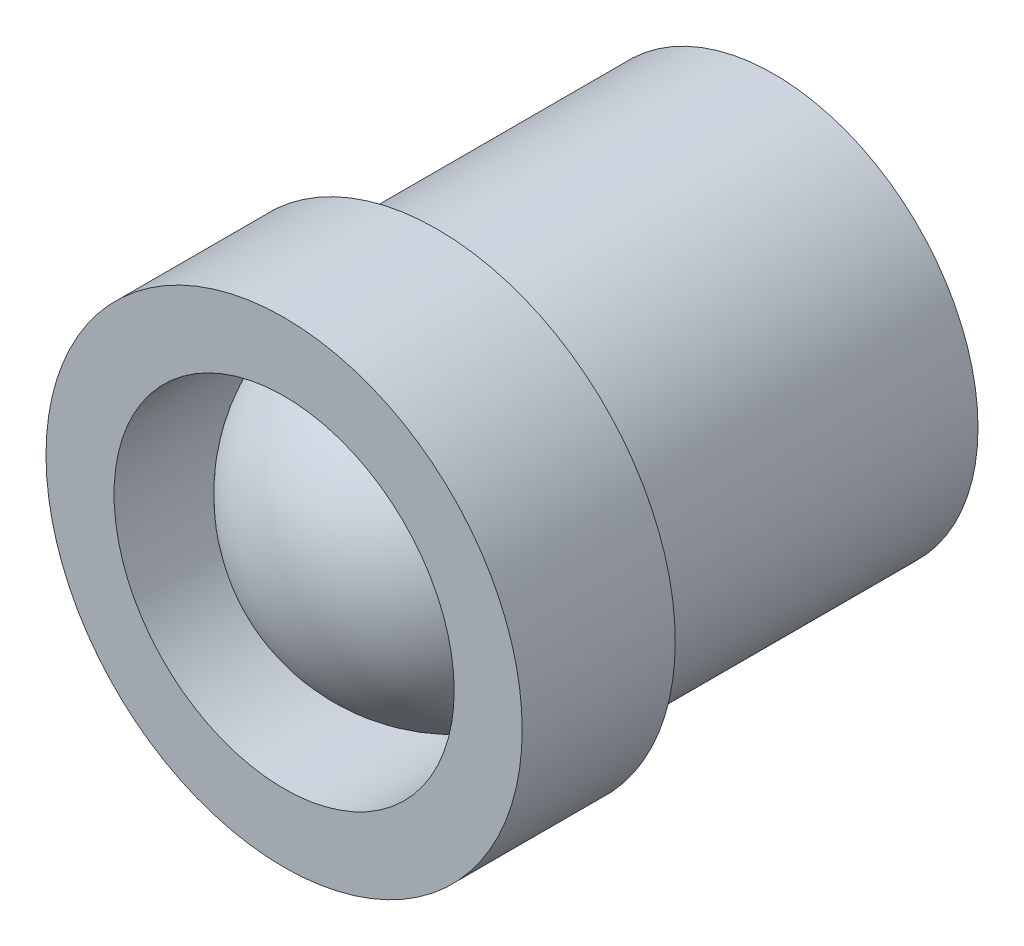
SolidWorks part; units mm, degrees
ref_plane "Front Plane" through (0, 0, 0) normal (0, 0, 1) x (1, 0, 0)
ref_plane "Top Plane" through (0, 0, 0) normal (0, 1, 0) x (1, 0, 0)
ref_plane "Right Plane" through (0, 0, 0) normal (1, 0, 0) x (0, 0, -1)
sketch "Sketch2" plane through (0, 0, 0) normal (0, 0, 1) x (1, 0, 0)
  circle A0 centre (0, 0) radius 6
  dimension "D1" = 12
extrude "Boss-Extrude1" add sketch "Sketch2" along normal mid plane 9.9
sketch "Sketch3" plane through (0, 0, 4.95) normal (0, 0, 1) x (1, 0, 0)
  circle A0 centre (0, 0) radius 7
  dimension "D1" = 14
extrude "Boss-Extrude2" add sketch "Sketch3" along normal blind 4.5
sketch "Sketch4" plane through (0, 0, 9.45) normal (0, 0, 1) x (1, 0, 0)
  circle A0 centre (0, 0) radius 5
  dimension "D1" = 10
extrude "Cut-Extrude1" cut sketch "Sketch4" against normal up to surface (14.4 mm away) up to face at (6, 0, -4.95)
sketch "Sketch6" plane through (0, 0, 0) normal (0, 1, 0) x (1, 0, 0)
  line L0 (0, -4.45) -> (0, -21.5384) construction
  line L2 (5, -4.45) -> (0, -4.45)
  line L3 (-5, -9.45) -> (5, -9.45) construction
  line L4 (5, -9.45) -> (5, 4.95) construction
  line L5 (0, -4.45) -> (0, -9.45)
  arc A0 (5, -4.45) -> (0, -9.45) centre (0, -4.45) cw
revolve "Revolve1" add sketch "Sketch6" angle 360 about L0
